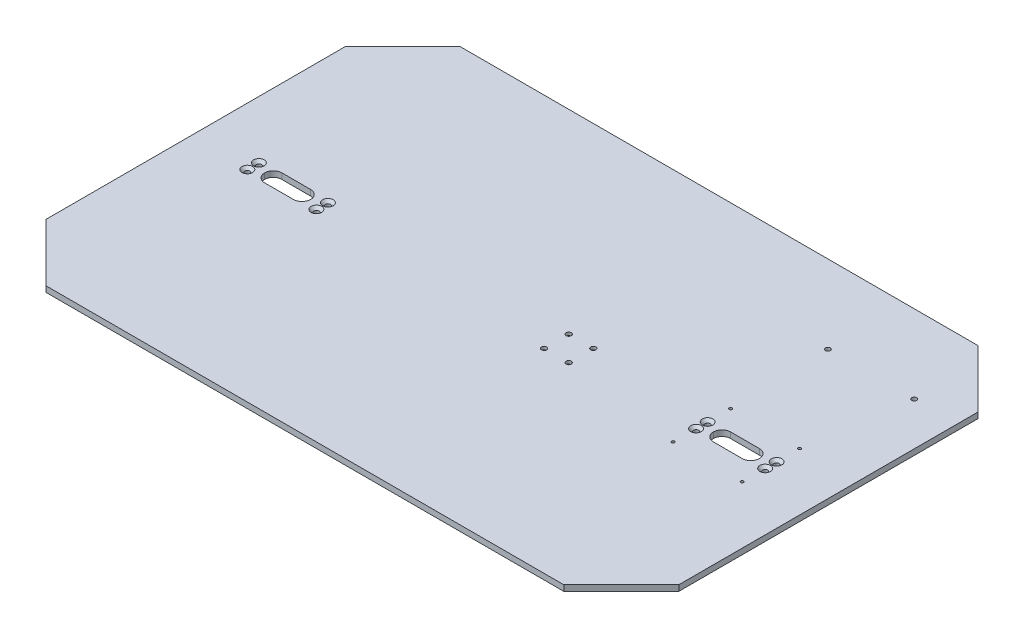
SolidWorks part; units mm, degrees
material "6063-T1"
ref_plane "Front Plane" through (0, 0, 0) normal (0, 0, 1) x (1, 0, 0)
ref_plane "Top Plane" through (0, 0, 0) normal (0, 1, 0) x (1, 0, 0)
ref_plane "Right Plane" through (0, 0, 0) normal (1, 0, 0) x (0, 0, -1)
sketch "Sketch1" plane through (0, 0, 0) normal (0, 1, 0) x (1, 0, 0)
  line L0 (-275, 0) -> (0, 0) construction
  line L1 (275, 180) -> (-275, 180)
  line L2 (275, 180) -> (275, -180)
  line L3 (275, -180) -> (-275, -180)
  line L4 (-275, 180) -> (-275, -180)
  line L5 (0, 0) -> (0, 180) construction
  dimension "D1" = 550
  dimension "D2" = 360
extrude "Boss-Extrude1" add sketch "Sketch1" along normal blind 5
sketch "Sketch2" plane through (0, 5, 0) normal (0, 1, 0) x (1, 0, 0)
  line L0 (215, 0) -> (275, 0) construction
  line L1 (215, 7.5) -> (175, 7.5)
  line L2 (215, 7.5) -> (215, -7.5)
  line L3 (215, -7.5) -> (175, -7.5)
  line L4 (175, 7.5) -> (175, -7.5)
  line L5 (275, -180) -> (275, 180) construction
  line L6 (0, 0) -> (0, 180) construction
  line L7 (275, 180) -> (-275, 180) construction
  line L8 (-215, 7.5) -> (-215, -7.5)
  line L9 (-215, 7.5) -> (-175, 7.5)
  line L10 (-175, 7.5) -> (-175, -7.5)
  line L11 (-215, -7.5) -> (-175, -7.5)
  dimension "D1" = 15
  dimension "D2" = 40
  dimension "D3" = 350
extrude "Cut-Extrude1" cut sketch "Sketch2" against normal blind 10
fillet "Fillet1" radius 7.5 8 edges at (-175, 2.5, 7.5) (-175, 2.5, -7.5) (-215, 2.5, -7.5) (-215, 2.5, 7.5) (175, 2.5, 7.5) (175, 2.5, -7.5) (215, 2.5, -7.5) (215, 2.5, 7.5)
chamfer "Chamfer1" distance 50 angle 45 4 edges at (-275, 2.5, 180) (275, 2.5, 180) (275, 2.5, -180) (-275, 2.5, -180)
sketch "Sketch8" plane through (0, 5, 0) normal (0, 1, 0) x (1, 0, 0)
  line L0 (175, 0) -> (215, 0) construction
  line L1 (195, 0) -> (195, 7.5) construction
  line L2 (207.5, 7.5) -> (182.5, 7.5) construction
  line L3 (0, 0) -> (0, -180) construction
  line L4 (-225, -180) -> (225, -180) construction
  line L5 (-195, 0) -> (-195, 7.5) construction
  line L6 (-175, 0) -> (-215, 0) construction
  circle A2 centre (225, 5) radius 1.5
  circle A3 centre (165, 5) radius 1.5
  circle A4 centre (165, -5) radius 1.5
  circle A5 centre (225, -5) radius 1.5
  circle A6 centre (-225, -5) radius 1.5
  circle A7 centre (-165, -5) radius 1.5
  circle A8 centre (-165, 5) radius 1.5
  circle A9 centre (-225, 5) radius 1.5
  dimension "D1" = 3
  dimension "D2" = 10
  dimension "D3" = 60
extrude "Cut-Extrude5" cut sketch "Sketch8" against normal blind 10
hole_wizard "CSK for M4 Hex Socket Countersunk Head Screw1" positions "3DSketch2" profile "Sketch9" countersink size "M4" standard "DIN" end condition through all
sketch3d "3DSketch2"
  line L0 (-225, 0, -5) -> (-225, 5, -5) construction
  line L1 (-225, 0, 5) -> (-225, 5, 5) construction
  line L2 (-165, 0, 5) -> (-165, 5, 5) construction
  line L3 (-165, 0, -5) -> (-165, 5, -5) construction
  line L4 (165, 0, 5) -> (165, 5, 5) construction
  line L5 (165, 0, -5) -> (165, 5, -5) construction
  line L6 (225, 0, -5) -> (225, 5, -5) construction
  line L7 (225, 0, 5) -> (225, 5, 5) construction
  point P0 (-225, 5, -5)
  point P4 (-225, 5, 5)
  point P8 (-165, 5, 5)
  point P12 (-165, 5, -5)
  point P16 (165, 5, 5)
  point P20 (165, 5, -5)
  point P24 (225, 5, -5)
  point P28 (225, 5, 5)
sketch "Sketch9" plane through (-225, 5, -5) normal (1, 0, 0) x (0, 0, 1)
  line L0 (0, 0) -> (0, 5)
  line L1 (0, 5) -> (2.25, 5)
  line L2 (2.25, 5) -> (2.25, 2.34)
  line L3 (2.25, 2.34) -> (4.59, 0)
  line L5 (4.59, 0) -> (0, 0)
  line L6 (-2.25, 2.34) -> (-4.59, 0) construction
  line L11 (0, -6.35) -> (0, 107.95) construction
  dimension "Thru Hole Dia." = 4.5
  dimension "Thru Hole Depth" = 5
  dimension "Near C'Sink Dia." = 9.18
  dimension "Near C'Sink Angle" = 90
sketch "Sketch10" plane through (0, 5, 0) normal (0, 1, 0) x (1, 0, 0)
  line L0 (237.5, 112) -> (162.5, 112) construction
  line L1 (200, 112) -> (200, 180) construction
  line L2 (225, 180) -> (-225, 180) construction
  line L3 (275, -130) -> (275, 130) construction
  circle A0 centre (237.5, 112) radius 2
  circle A1 centre (162.5, 112) radius 2
  dimension "D2" = 4
  dimension "D1" = 75
  dimension "D3" = 75
  dimension "D4" = 68
extrude "Cut-Extrude6" cut sketch "Sketch10" against normal blind 10
hole_wizard "M5 Tapped Hole1" positions "3DSketch3" profile "Sketch13" tap size "M5" standard "DIN"
sketch3d "3DSketch3"
  line L0 (237.5, 0, -112) -> (237.5, 5, -112) construction
  line L1 (162.5, 0, -112) -> (162.5, 5, -112) construction
  point P0 (237.5, 5, -112)
  point P4 (162.5, 5, -112)
sketch "Sketch13" plane through (237.5, 5, -112) normal (1, 0, 0) x (0, 0, 1)
  line L0 (0, 0) -> (0, 13.6618)
  line L1 (0, 13.6618) -> (2.1, 12.4)
  line L2 (2.1, 12.4) -> (2.1, 0)
  line L5 (2.1, 0) -> (0, 0)
  line L10 (0, 13.6618) -> (-2.1, 12.4) construction
  line L11 (0, -6.35) -> (0, 107.95) construction
  dimension "Tap Drill Dia." = 4.2
  dimension "Tap Drill Depth" = 12.4
  dimension "Drill Angle" = 118
cosmetic thread "Hole Thread1" parameters "D1"=6, "D2"=5
cosmetic thread "Hole Thread2" parameters "D1"=6, "D2"=5
sketch "Sketch14" plane through (0, 5, 0) normal (0, 1, 0) x (-1, 0, 0)
  line L0 (-175, 0) -> (-215, 0) construction
  line L1 (-225, 5) -> (-225, 25) construction
  line L2 (-195, -7.5) -> (-195, 0) construction
  line L3 (-207.5, -7.5) -> (-182.5, -7.5) construction
  line L4 (-225, -5) -> (-225, -25) construction
  circle A0 centre (-225, 25) radius 1.25
  circle A1 centre (-225, -25) radius 1.25
  circle A2 centre (-165, 25) radius 1.25
  circle A3 centre (-165, -25) radius 1.25
  dimension "D1" = 50
  dimension "D2" = 2.5
extrude "Cut-Extrude8" cut sketch "Sketch14" against normal up to next
cosmetic thread "Hole Thread3" parameters "D1"=5, "D2"=3
cosmetic thread "Hole Thread4" parameters "D1"=5, "D2"=3
cosmetic thread "Hole Thread5" parameters "D1"=5, "D2"=3
cosmetic thread "Hole Thread6" parameters "D1"=5, "D2"=3
hole_wizard "M3 Tapped Hole1" positions "3DSketch4" profile "Sketch15" tap size "M3" standard "DIN"
sketch3d "3DSketch4"
  line L0 (225, 0, 25) -> (225, 5, 25) construction
  line L1 (165, 0, 25) -> (165, 5, 25) construction
  line L2 (165, 0, -25) -> (165, 5, -25) construction
  line L3 (225, 0, -25) -> (225, 5, -25) construction
  point P0 (225, 5, 25)
  point P4 (165, 5, 25)
  point P8 (165, 5, -25)
  point P12 (225, 5, -25)
sketch "Sketch15" plane through (225, 5, 25) normal (1, 0, 0) x (0, 0, 1)
  line L0 (0, 0) -> (0, 8.2511)
  line L1 (0, 8.2511) -> (1.25, 7.5)
  line L2 (1.25, 7.5) -> (1.25, 0)
  line L5 (1.25, 0) -> (0, 0)
  line L10 (0, 8.2511) -> (-1.25, 7.5) construction
  line L11 (0, -6.35) -> (0, 107.95) construction
  dimension "Tap Drill Dia." = 2.5
  dimension "Tap Drill Depth" = 7.5
  dimension "Drill Angle" = 118
cosmetic thread "Hole Thread7" parameters "D1"=5, "D2"=3
cosmetic thread "Hole Thread8" parameters "D1"=5, "D2"=3
cosmetic thread "Hole Thread9" parameters "D1"=5, "D2"=3
cosmetic thread "Hole Thread10" parameters "D1"=5, "D2"=3
sketch "Sketch16" plane through (0, 5, 0) normal (0, 1, 0) x (1, 0, 0)
  line L0 (60, 0) -> (275, 0) construction
  line L1 (38.6, 10.7) -> (60, 10.7) construction
  line L2 (38.6, 10.7) -> (38.6, -10.7) construction
  line L3 (38.6, -10.7) -> (60, -10.7) construction
  line L4 (60, 10.7) -> (60, -10.7) construction
  line L5 (275, -130) -> (275, 130) construction
  circle A0 centre (38.6, 10.7) radius 1.5
  circle A1 centre (60, 10.7) radius 1.5
  circle A2 centre (38.6, -10.7) radius 1.5
  circle A3 centre (60, -10.7) radius 1.5
  dimension "D2" = 3
  dimension "D1" = 21.4
  dimension "D3" = 215
extrude "Cut-Extrude9" cut sketch "Sketch16" against normal through all
hole_wizard "CSK for M4 Hex Socket Countersunk Head Screw2" positions "3DSketch5" profile "Sketch17" countersink size "M4" standard "DIN" end condition through all
sketch3d "3DSketch5"
  line L0 (60, 0, -10.7) -> (60, 5, -10.7) construction
  line L1 (38.6, 0, -10.7) -> (38.6, 5, -10.7) construction
  line L2 (38.6, 0, 10.7) -> (38.6, 5, 10.7) construction
  line L3 (60, 0, 10.7) -> (60, 5, 10.7) construction
  point P0 (60, 0, -10.7)
  point P4 (38.6, 0, -10.7)
  point P8 (38.6, 0, 10.7)
  point P12 (60, 0, 10.7)
sketch "Sketch17" plane through (60, 0, -10.7) normal (1, 0, 0) x (0, 0, -1)
  line L0 (0, 0) -> (0, 5)
  line L1 (0, 5) -> (2.25, 5)
  line L2 (2.25, 5) -> (2.25, 2.34)
  line L3 (2.25, 2.34) -> (4.59, 0)
  line L5 (4.59, 0) -> (0, 0)
  line L6 (-2.25, 2.34) -> (-4.59, 0) construction
  line L11 (0, -6.35) -> (0, 107.95) construction
  dimension "Thru Hole Dia." = 4.5
  dimension "Thru Hole Depth" = 5
  dimension "Near C'Sink Dia." = 9.18
  dimension "Near C'Sink Angle" = 90
